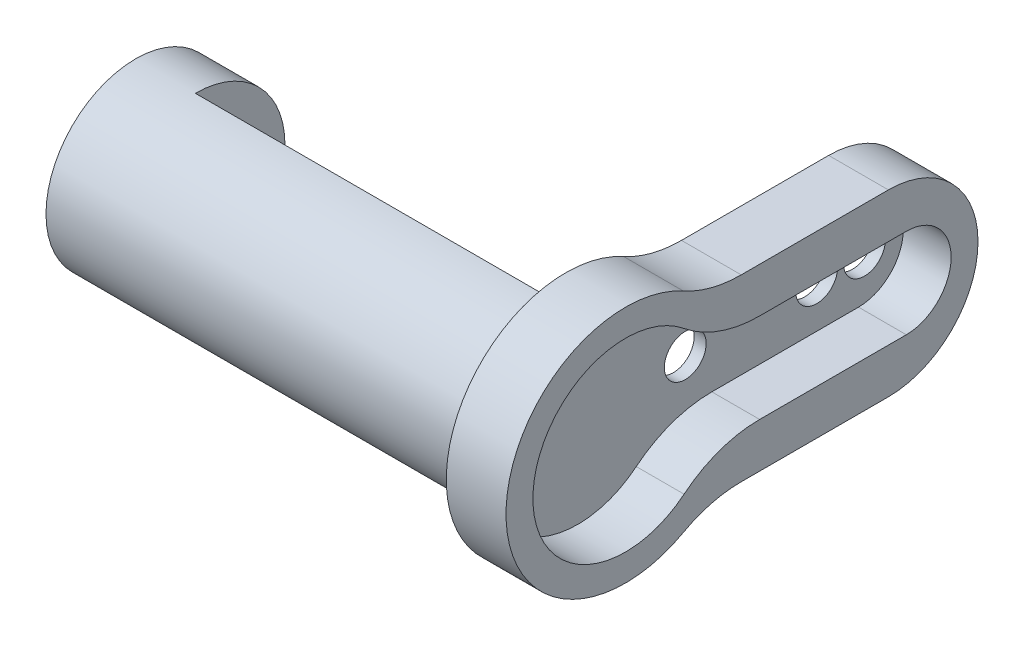
SolidWorks part; units mm, degrees
ref_plane "Front Plane" through (0, 0, 0) normal (0, 0, 1) x (1, 0, 0)
ref_plane "Top Plane" through (0, 0, 0) normal (0, 1, 0) x (1, 0, 0)
ref_plane "Right Plane" through (0, 0, 0) normal (1, 0, 0) x (0, 0, -1)
sketch "Sketch1" plane through (0, 0, 0) normal (1, 0, 0) x (0, 0, -1)
  circle A0 centre (0, 0) radius 7.5
  dimension "D1" = 15
extrude "Boss-Extrude1" add sketch "Sketch1" along normal mid plane 36
sketch "Sketch2" plane through (18, 0, 0) normal (1, 0, 0) x (0, 0, -1)
  line L0 (0, 0) -> (22, 0) construction
  line L1 (0, 7.5) -> (22, 7.5)
  line L2 (0, -7.5) -> (22, -7.5)
  arc A0 (22, -7.5) -> (22, 7.5) centre (22, 0) ccw
  circle A1 centre (0, 0) radius 7.5 construction
  circle A3 centre (0, 0) radius 7.5
  arc A4 (0, 7.5) -> (0, -7.5) centre (0, 0) ccw
  dimension "D2" = 15
  dimension "D1" = 22
  dimension "D3" = 0
extrude "Boss-Extrude2" add sketch "Sketch2" against normal blind 5
sketch "Sketch3" plane through (18, 0, 0) normal (1, 0, 0) x (0, 0, -1)
  circle A0 centre (0, 0) radius 10
  dimension "D1" = 20
extrude "Boss-Extrude3" add sketch "Sketch3" against normal up to surface (5 mm away) up to face at (13, 0, -14.75)
fillet "Fillet1" radius 10 2 edges at (15.5, -7.5, -6.6144) (15.5, 7.5, -6.6144)
sketch "Sketch4" plane through (18, 0, 0) normal (1, 0, 0) x (0, 0, -1)
  line L0 (-7.75, 0) -> (27.25, 0) construction
  line L1 (23.5, 3.75) -> (11.225, 3.75)
  line L2 (23.5, -3.75) -> (11.225, -3.75)
  arc A0 (4.901, 6.0035) -> (4.901, -6.0035) centre (0, 0) ccw
  arc A1 (23.5, -3.75) -> (23.5, 3.75) centre (23.5, 0) ccw
  arc A2 (11.225, -3.75) -> (4.901, -6.0035) centre (11.225, -13.75) ccw
  arc A3 (11.225, 3.75) -> (4.901, 6.0035) centre (11.225, 13.75) cw
  dimension "D1" = 15.5
  dimension "D3" = 7.5
  dimension "D4" = 10
  dimension "D2" = 35
extrude "Cut-Extrude1" cut sketch "Sketch4" against normal blind 4
sketch "Sketch5" plane through (14, 0, 0) normal (1, 0, 0) x (0, 0, -1)
  line L0 (0, 0) -> (27.25, 0) construction
  arc A0 (23.5, -3.75) -> (23.5, 3.75) centre (23.5, 0) ccw construction
  circle A1 centre (24, 0) radius 1.75
  circle A2 centre (20, 0) radius 1.75
  circle A3 centre (9, 0) radius 1.75
  point P13 (0, 0)
  point P14 (24.0005, 0)
  point P15 (24.6985, 0)
  point P18 (22.651, 0)
  dimension "D1" = 3.5
  dimension "D2" = 4
  dimension "D3" = 3.5
  dimension "D4" = 3.5
  dimension "D5" = 11
  dimension "D6" = 0.5
extrude "Cut-Extrude2" cut sketch "Sketch5" against normal blind 24
sketch "Sketch6" plane through (-18, 0, 0) normal (-1, 0, 0) x (0, 0, 1)
  line L0 (0, 7.5) -> (0, -7.5)
  circle A0 centre (0, 0) radius 7.5 construction
  circle A1 centre (0, 0) radius 7.5 construction
  circle A3 centre (0, 0) radius 7.5
  arc A4 (0, 7.5) -> (0, -7.5) centre (0, 0) ccw
  dimension "D1" = 0
extrude "Cut-Extrude3" cut sketch "Sketch6" against normal up to surface (31 mm away) up to face at (13, 0, -25.75)
sketch "Sketch7" plane through (-18, 0, 0) normal (-1, 0, 0) x (0, 0, 1)
  circle A0 centre (0, 0) radius 7.5
  arc A1 (0, -7.5) -> (0, 7.5) centre (0, 0) ccw construction
extrude "Boss-Extrude4" add sketch "Sketch7" along normal blind 5
